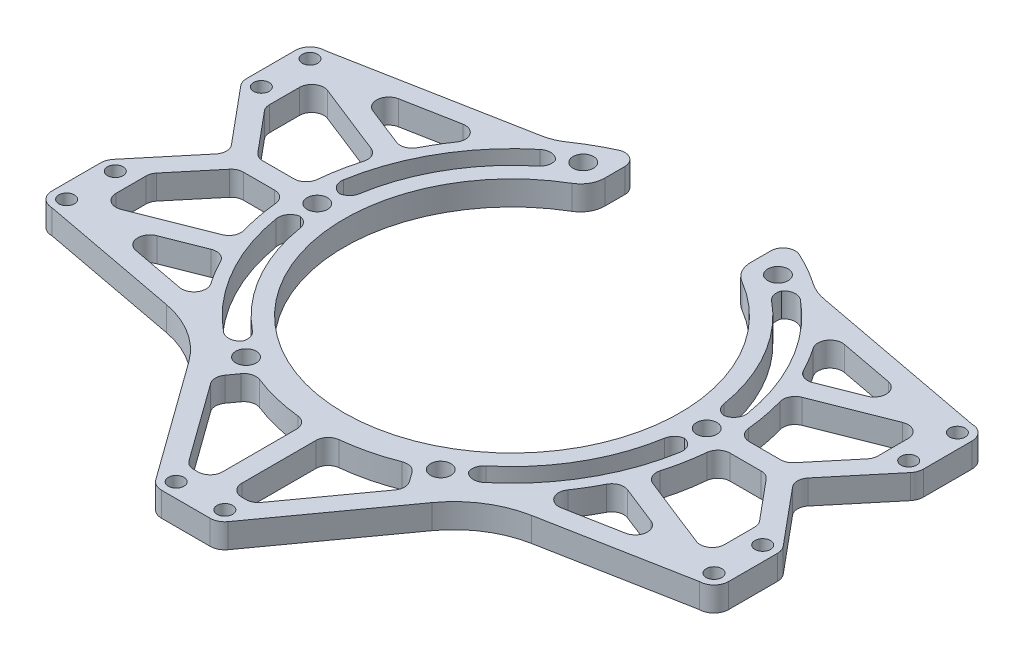
SolidWorks part; units mm, degrees
ref_plane "前视基准面" through (0, 0, 0) normal (0, 0, 1) x (1, 0, 0)
ref_plane "上视基准面" through (0, 0, 0) normal (0, 1, 0) x (1, 0, 0)
ref_plane "右视基准面" through (0, 0, 0) normal (1, 0, 0) x (0, 0, -1)
other "Configuration Table"
sketch "草图1" plane through (0, 0, 0) normal (0, 1, 0) x (1, 0, 0)
  line L0 (0, 0) -> (0, 40) construction
  line L1 (0, 0) -> (20, 34.641) construction
  line L2 (-15, 41.8957) -> (-15, 31.0685)
  line L3 (15, 41.8957) -> (15, 31.0685)
  circle A0 centre (0, 0) radius 40 construction
  circle A1 centre (20, 34.641) radius 2.1
  circle A2 centre (40, 0) radius 2.1
  circle A3 centre (20, -34.641) radius 2.1
  circle A4 centre (-20, -34.641) radius 2.1
  circle A5 centre (-40, 0) radius 2.1
  circle A6 centre (-20, 34.641) radius 2.1
  circle A7 centre (0, 0) radius 44.5
  circle A8 centre (0, 0) radius 34.5
  point P18 (0, 0)
  dimension "D1" = 80
  dimension "D3" = 4.2
  dimension "D5" = 89
  dimension "D6" = 69
  dimension "D2" = 30
  dimension "D7" = 15
  dimension "D8" = 15
  dimension "D4" = 6
extrude "凸台-拉伸1" add sketch "草图1" along normal blind 5 contours A8 L2 A7 L3 A1 A2 A3 A4 A5 A6 region at (-16.2404, 0, -36.4821)
sketch "草图2" plane through (0, 5, 0) normal (0, 1, 0) x (1, 0, 0)
  line L0 (-66.5, 0) -> (66.5, 0) construction
  line L1 (66.5, 0) -> (66.5, 15) construction
  line L2 (66.5, 15) -> (66.5, 25) construction
  line L3 (0, 0) -> (0, -44.5) construction
  line L4 (-66.5, 15) -> (-66.5, 25) construction
  line L5 (-66.5, 0) -> (-66.5, 15) construction
  line L6 (63.5, 25) -> (63.5, 15)
  line L7 (69.5, 25) -> (69.5, 15)
  line L8 (66.5, 28) -> (26.8536, 35.4843)
  line L9 (68.8052, 13.0801) -> (34.1943, -28.4781)
  line L10 (68.8052, -13.0801) -> (34.1943, 28.4781)
  line L11 (69.5, -25) -> (69.5, -15)
  line L12 (66.5, -28) -> (26.8536, -35.4843)
  line L13 (-66.5, 15) -> (-66.5, 25) construction
  line L14 (-66.5, 0) -> (-66.5, 15) construction
  line L15 (-66.5, -28) -> (-26.8536, -35.4843)
  line L16 (-69.5, -25) -> (-69.5, -15)
  line L17 (-68.8052, -13.0801) -> (-34.1943, 28.4781)
  line L18 (-68.8052, 13.0801) -> (-34.1943, -28.4781)
  line L19 (-66.5, 28) -> (-26.8536, 35.4843)
  line L20 (-69.5, 25) -> (-69.5, 15)
  line L21 (-63.5, 25) -> (-63.5, 15)
  circle A0 centre (66.5, 15) radius 1.6
  circle A1 centre (66.5, 25) radius 1.6
  circle A2 centre (66.5, -15) radius 1.6
  circle A3 centre (66.5, -25) radius 1.6
  arc A4 (-15, 41.8957) -> (15, 41.8957) centre (0, 0) ccw construction
  circle A5 centre (-66.5, -25) radius 1.6
  circle A6 centre (-66.5, -15) radius 1.6
  circle A7 centre (-66.5, 25) radius 1.6
  circle A8 centre (-66.5, 15) radius 1.6
  circle A9 centre (66.5, 25) radius 3
  circle A10 centre (66.5, 15) radius 3
  circle A11 centre (20, 34.641) radius 2.1 construction
  circle A12 centre (66.5, -15) radius 3
  circle A13 centre (66.5, -25) radius 3
  circle A14 centre (-66.5, -25) radius 3
  circle A15 centre (-66.5, -15) radius 3
  circle A16 centre (-66.5, 15) radius 3
  circle A17 centre (-66.5, 25) radius 3
  circle A18 centre (-66.5, -25) radius 1.6
  circle A19 centre (-66.5, -15) radius 1.6
  circle A20 centre (-66.5, 25) radius 1.6
  circle A21 centre (-66.5, 15) radius 1.6
  circle A22 centre (0, 0) radius 44.5
  point P4 (0, 0)
  arc M10 (-15, 41.8957) -> (15, 41.8957) centre (0, 0) ccw
  dimension "D4" = 3.2
  dimension "D5" = 3.2
  dimension "D6" = 6
  dimension "D7" = 6
  dimension "D8" = 89
  dimension "D1" = 133
  dimension "D2" = 15
  dimension "D3" = 10
extrude "凸台-拉伸2" add sketch "草图2" against normal blind 5 contours L19 A17 L21 A16 L18 L17 M10 | L17 L18 M10 | A15 L16 A14 L15 L18 L17 M10 | A17 A7 | L21 A17 L20 A16 | A16 A8 | A15 A6 | A14 A5 | A9 A1 | A10 L7 A9 L6 | A10 A0 | A10 L6 A9 L8 L10 L9 M10 | L9 L10 M10 | L12 A13 L11 A12 L10 L9 M10 | A12 A2 | A13 A3 region at (66.5, 5, -20) region at (51.5126, 5, -20.1149) region at (64.4387, 5, -27.0613) region at (66.5, 5, -17.9151) region at (52.2688, 5, 20.1091) region at (47.5774, 5, 0) region at (69.2412, 5, 14.008) region at (-51.5126, 5, -20.1149) region at (64.4387, 5, 22.9387) region at (-52.2688, 5, 20.1091) region at (-64.4387, 5, -27.0613) region at (-47.5774, 5, 0) region at (-68.5613, 5, 27.0613) region at (-66.5, 5, -20) region at (-65.508, 5, -12.2588) region at (-65.508, 5, 12.2588)
sketch "草图3" plane through (0, 5, 0) normal (0, 1, 0) x (1, 0, 0)
  line L0 (-62.5, 24.6845) -> (-62.5, 11.7597)
  line L1 (-62.5, 11.7597) -> (-52.7062, 0)
  line L2 (-52.7062, 0) -> (-62.5, -11.7597)
  line L3 (-62.5, -11.7597) -> (-62.5, -24.6845)
  line L4 (-62.5, -24.6845) -> (-32.5562, -30.3371)
  line L5 (-62.5, 24.6845) -> (-32.5562, 30.3371)
  line L6 (-66.5, 28) -> (-26.8536, 35.4843) construction
  line L7 (-68.8052, 13.0801) -> (-57.9117, 0) construction
  line L8 (-68.8052, -13.0801) -> (-57.9117, 0) construction
  line L9 (-66.5, -28) -> (-26.8536, -35.4843) construction
  line L10 (54.3718, -2) -> (44.455, -2)
  line L11 (0, 44.5) -> (0, -44.5) construction
  line L12 (62.5, 24.6845) -> (32.5562, 30.3371)
  line L13 (62.5, -24.6845) -> (32.5562, -30.3371)
  line L14 (62.5, -11.7597) -> (62.5, -24.6845)
  line L15 (52.7062, 0) -> (62.5, -11.7597)
  line L16 (62.5, 11.7597) -> (52.7062, 0)
  line L17 (62.5, 24.6845) -> (62.5, 11.7597)
  line L18 (-52.7062, 0) -> (-44.5, 0)
  line L19 (-62.5, 24.6845) -> (0, 0)
  line L20 (0, 0) -> (-62.5, -24.6845)
  line L21 (-63.2347, 22.8243) -> (-5.4446, 0)
  line L22 (-5.4446, 0) -> (-63.2347, -22.8243)
  line L23 (-54.3718, -2) -> (-44.455, -2)
  line L24 (-61.7653, 26.5446) -> (5.4446, 0)
  line L25 (5.4446, 0) -> (-61.7653, -26.5446)
  line L26 (-54.3718, 2) -> (-44.455, 2)
  line L27 (-52.7062, 2) -> (-44.5, 2) construction
  line L28 (-52.7062, -2) -> (-44.5, -2) construction
  line L29 (54.3718, 2) -> (44.455, 2)
  line L30 (0, 0) -> (62.5, 24.6845)
  line L31 (0, 0) -> (62.5, -24.6845)
  line L32 (5.4446, 0) -> (63.2347, -22.8243)
  line L33 (5.4446, 0) -> (63.2347, 22.8243)
  line L34 (-5.4446, 0) -> (61.7653, -26.5446)
  line L35 (-5.4446, 0) -> (61.7653, 26.5446)
  circle A0 centre (0, 0) radius 44.5
  circle A1 centre (-66.5, 25) radius 1.6 construction
  circle A2 centre (-66.5, -15) radius 1.6 construction
  dimension "D1" = 89
  dimension "D2" = 4
  dimension "D3" = 4
  dimension "D4" = 4
  dimension "D5" = 4
  dimension "D6" = 4
  dimension "D7" = 4
  dimension "D8" = 2
  dimension "D10" = 2
  dimension "D9" = 2
  dimension "D11" = 2
extrude "切除-拉伸1" cut sketch "草图3" against normal blind 5 contours A0 L5 L24 | A0 L21 L0 L1 L26 | A0 L23 L2 L3 L22 | A0 L25 L4 | A0 L35 L12 | A0 L29 L16 L17 L33 | A0 L32 L14 L15 L10 | A0 L13 L34 region at (-52.8513, 5, -11.4059) region at (-44.3103, 5, -24.6462) region at (44.3103, 5, -24.6462) region at (-52.8513, 5, 11.4059) region at (-44.3103, 5, 24.6462) region at (44.3103, 5, 24.6462) region at (52.8513, 5, -11.4059) region at (52.8513, 5, 11.4059)
fillet "圆角1" radius 5 2 edges at (15, 2.5, -31.0685) (-15, 2.5, -31.0685)
fillet "圆角2" radius 2.5 35 edges at (58.8162, 2.5, 25.3799) (40.6124, 2.5, 18.1902) (32.5562, 2.5, 30.3371) (62.5, 2.5, 22.5341) (62.5, 2.5, 11.7597) (54.3718, 2.5, 2) (42.0817, 2.5, 14.4699) (44.455, 2.5, 2) (62.5, 2.5, -11.7597) (54.3718, 2.5, -2) (44.455, 2.5, -2) (42.0817, 2.5, -14.4699) (62.5, 2.5, -22.5341) (40.6124, 2.5, -18.1902) (32.5562, 2.5, -30.3371) (58.8162, 2.5, -25.3799) (-57.9117, 2.5, 0) (-58.8162, 2.5, 25.3799) (-40.6124, 2.5, 18.1902) (-32.5562, 2.5, 30.3371) (-62.5, 2.5, 11.7597) (-62.5, 2.5, 22.5341) (-54.3718, 2.5, 2) (-44.455, 2.5, 2) (-42.0817, 2.5, 14.4699) (-54.3718, 2.5, -2) (-44.455, 2.5, -2) (-42.0817, 2.5, -14.4699) (-62.5, 2.5, -11.7597) (-62.5, 2.5, -22.5341) (-40.6124, 2.5, -18.1902) (-32.5562, 2.5, -30.3371) (-58.8162, 2.5, -25.3799) (15, 2.5, -41.8957) (-15, 2.5, -41.8957)
fillet "圆角3" radius 10 4 edges at (-26.8536, 2.5, -35.4843) (-26.8536, 2.5, 35.4843) (26.8536, 2.5, 35.4843) (26.8536, 2.5, -35.4843)
sketch "草图4" plane through (0, 5, 0) normal (0, 1, 0) x (1, 0, 0)
  line L0 (0, 0) -> (0, -64)
  line L1 (0, -64) -> (5, -64)
  line L2 (0, -64) -> (-5, -64)
  line L3 (-5, -67) -> (5, -67)
  line L4 (-36.0884, -26.0361) -> (-7.4329, -65.7552)
  line L5 (36.0884, -26.0361) -> (7.4329, -65.7552)
  circle A0 centre (5, -64) radius 1.6
  circle A1 centre (-5, -64) radius 1.6
  circle A2 centre (-5, -64) radius 3
  circle A3 centre (5, -64) radius 3
  arc A4 (-25.2247, -36.6601) -> (25.2247, -36.6601) centre (0, 0) ccw construction
  circle A5 centre (0, 0) radius 34.5
  circle A6 centre (0, 0) radius 44.5
  dimension "D2" = 5
  dimension "D4" = 3.2
  dimension "D5" = 3.2
  dimension "D6" = 6
  dimension "D7" = 6
  dimension "D8" = 69
  dimension "D9" = 89
  dimension "D1" = 64
  dimension "D3" = 5
extrude "凸台-拉伸4" add sketch "草图4" against normal blind 5 contours A6 L0 L1 A3 L5 | A6 L4 A2 L2 L0 | A3 L1 L2 A2 L3 | A2 A1 | A3 A0 region at (11.0941, 5, 49.9144) region at (-11.0941, 5, 49.9144) region at (0, 5, 65.7021) region at (5, 5, 61.0849) region at (-2.9387, 5, 66.0613)
sketch "草图5" plane through (0, 5, 0) normal (0, 1, 0) x (1, 0, 0)
  line L0 (-6.6527, -60) -> (6.6527, -60)
  line L1 (-6.6527, -60) -> (-20.0078, -41.4886)
  line L2 (-20.0078, -41.4886) -> (-16.3976, -36.4845)
  line L5 (29.6532, -34.9558) -> (7.4329, -65.7552) construction
  line L6 (-29.6532, -34.9558) -> (-7.4329, -65.7552) construction
  line L7 (0, -40) -> (0, -67) construction
  line L8 (-5, -67) -> (5, -67) construction
  line L9 (6.6527, -60) -> (20.0078, -41.4886)
  line L10 (20.0078, -41.4886) -> (16.3976, -36.4845)
  line L11 (-2, -39.95) -> (-2, -67)
  line L12 (2, -39.95) -> (2, -67)
  line L13 (-2, -40) -> (-2, -67) construction
  line L14 (2, -40) -> (2, -67) construction
  circle A0 centre (0, 0) radius 40
  circle A1 centre (-5, -64) radius 1.6 construction
  circle A2 centre (-20, -34.641) radius 2.1 construction
  point P22 (0, -60)
  dimension "D1" = 4
  dimension "D2" = 4
  dimension "D3" = 4
  dimension "D4" = 2
  dimension "D5" = 2
extrude "切除-拉伸2" cut sketch "草图5" against normal blind 5 contours A0 L2 L1 L0 L11 | A0 L12 L0 L9 L10 region at (-9.0105, 5, 47.2065) region at (9.0105, 5, 47.2065)
fillet "圆角4" radius 2.5 10 edges at (-6.6527, 2.5, 60) (-2, 2.5, 60) (-20.0078, 2.5, 41.4886) (-16.3976, 2.5, 36.4845) (-2, 2.5, 39.95) (2, 2.5, 60) (6.6527, 2.5, 60) (2, 2.5, 39.95) (20.0078, 2.5, 41.4886) (16.3976, 2.5, 36.4845)
sketch "草图6" plane through (0, 5, 0) normal (0, 1, 0) x (1, 0, 0)
  line L0 (-41.9095, 4) -> (-37.6883, 4)
  line L1 (-41.9095, -4) -> (-37.6883, -4)
  line L2 (-17.4907, 38.2947) -> (-15.3801, 34.639)
  line L3 (-24.4189, 34.2947) -> (-22.3083, 30.639)
  line L4 (24.4189, 34.2947) -> (22.3083, 30.639)
  line L5 (17.4907, 38.2947) -> (15.3801, 34.639)
  line L6 (41.9095, -4) -> (37.6883, -4)
  line L7 (41.9095, 4) -> (37.6883, 4)
  line L8 (17.4907, -38.2947) -> (15.3801, -34.639)
  line L9 (24.4189, -34.2947) -> (22.3083, -30.639)
  line L10 (-24.4189, -34.2947) -> (-22.3083, -30.639)
  line L11 (-17.4907, -38.2947) -> (-15.3801, -34.639)
  line L12 (-37.6883, 4) -> (0, 0) construction
  circle A0 centre (0, 0) radius 42.1
  circle A1 centre (0, 0) radius 37.9
  circle A2 centre (-40, 0) radius 2.1 construction
  point P32 (0, 0)
  dimension "D1" = 84.2
  dimension "D2" = 75.8
  dimension "D3" = 4
  dimension "D4" = 4
  dimension "D5" = 6
extrude "切除-拉伸3" cut sketch "草图6" against normal blind 5 contours A1 L3 A0 L0 | A1 L1 A0 L10 | A1 L7 A0 L4 | A1 L9 A0 L6 region at (-33.6527, 5, -19.4294) region at (-33.6527, 5, 19.4294) region at (33.6527, 5, -19.4294) region at (33.6527, 5, 19.4294)
fillet "圆角6" radius 2.5 16 edges at (22.3083, 2.5, -30.639) (24.4189, 2.5, -34.2947) (37.6883, 2.5, -4) (41.9095, 2.5, -4) (37.6883, 2.5, 4) (41.9095, 2.5, 4) (22.3083, 2.5, 30.639) (24.4189, 2.5, 34.2947) (-24.4189, 2.5, 34.2947) (-22.3083, 2.5, 30.639) (-41.9095, 2.5, 4) (-37.6883, 2.5, 4) (-41.9095, 2.5, -4) (-37.6883, 2.5, -4) (-22.3083, 2.5, -30.639) (-24.4189, 2.5, -34.2947)
fillet "圆角8" radius 20 2 edges at (29.6532, 2.5, 34.9558) (-29.6532, 2.5, 34.9558)
fillet "圆角9" radius 2.5 1 edges at (57.9117, 2.5, 0)
